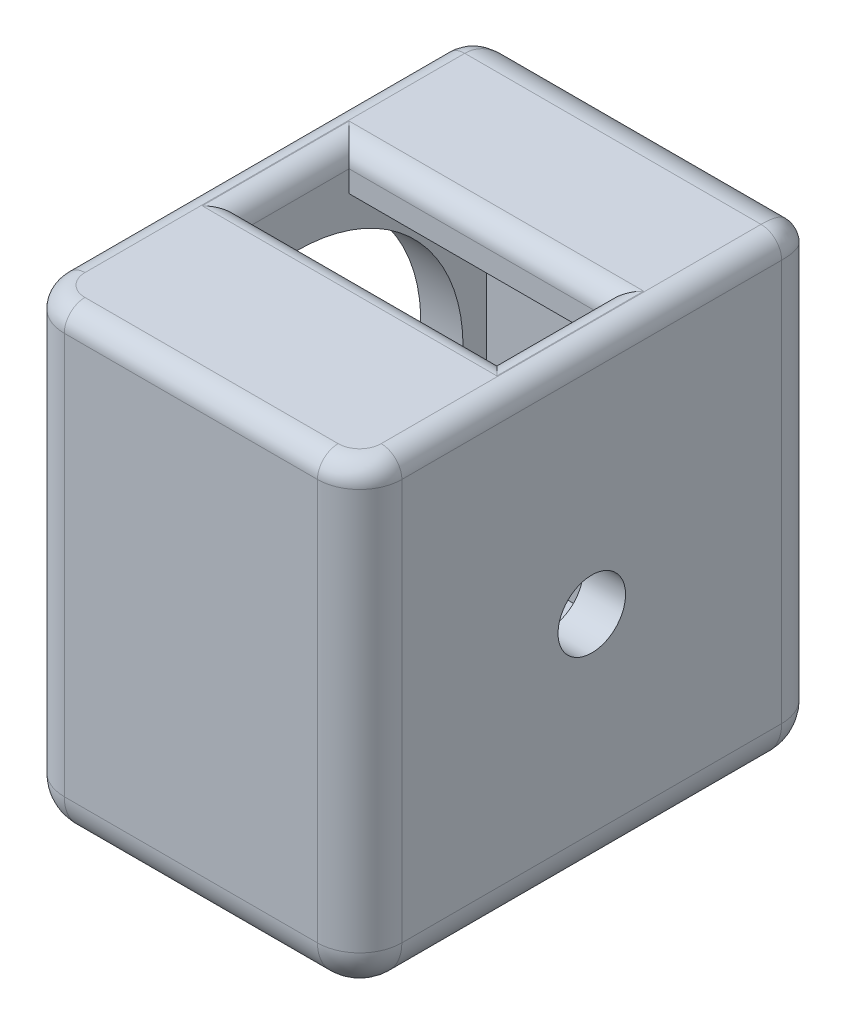
SolidWorks part; units mm, degrees
material "POLYURETHANE (11671)"
ref_plane "Front Plane" through (0, 0, 0) normal (0, 0, 1) x (1, 0, 0)
ref_plane "Top Plane" through (0, 0, 0) normal (0, 1, 0) x (1, 0, 0)
ref_plane "Right Plane" through (0, 0, 0) normal (1, 0, 0) x (0, 0, -1)
sketch "Sketch2" plane through (0, 0, 0) normal (0, 1, 0) x (1, 0, 0)
  line L0 (-7.62, 11.43) -> (-7.62, 13.97) construction
  line L1 (7.62, 11.43) -> (-7.62, 11.43)
  line L2 (7.62, 11.43) -> (7.62, -11.43)
  line L3 (7.62, -11.43) -> (-7.62, -11.43)
  line L4 (-7.62, 11.43) -> (-7.62, -11.43)
  line L5 (10.16, 13.97) -> (-10.16, 13.97)
  line L6 (10.16, 13.97) -> (10.16, -13.97)
  line L7 (10.16, -13.97) -> (-10.16, -13.97)
  line L8 (-10.16, 13.97) -> (-10.16, -13.97)
  line L9 (-7.62, 11.43) -> (-10.16, 11.43) construction
  point P8 (0, 13.97)
  point P9 (0, 11.43)
  point P11 (-7.62, 0)
  point P12 (-10.16, 0)
  dimension "D1" = 15.24
  dimension "D2" = 22.86
  dimension "D3" = 2.54
extrude "Boss-Extrude1" add sketch "Sketch2" along normal mid plane 27.94
sketch "Sketch3" plane through (0, -13.97, 0) normal (0, -1, 0) x (1, 0, 0)
  line L1 (-7.62, 11.43) -> (7.62, 11.43)
  line L2 (-7.62, 11.43) -> (-7.62, -11.43)
  line L3 (-7.62, -11.43) -> (7.62, -11.43)
  line L4 (7.62, 11.43) -> (7.62, -11.43)
extrude "Boss-Extrude2" add sketch "Sketch3" against normal blind 2.54
sketch "Sketch4" plane through (0, 13.97, 0) normal (0, 1, 0) x (1, 0, 0)
  line L0 (7.62, -11.43) -> (7.62, 11.43) construction
  line L1 (-7.62, 11.43) -> (7.62, 11.43)
  line L2 (-7.62, 11.43) -> (-7.62, 3.175)
  line L3 (-7.62, 3.175) -> (7.62, 3.175)
  line L4 (7.62, 11.43) -> (7.62, 3.175)
  line L11 (-7.62, -11.43) -> (7.62, -11.43) construction
  line L12 (-7.62, -11.43) -> (7.62, -11.43)
  line L13 (-7.62, -11.43) -> (-7.62, -3.175)
  line L14 (-7.62, -3.175) -> (7.62, -3.175)
  line L15 (7.62, -11.43) -> (7.62, -3.175)
  line L16 (7.62, -11.43) -> (-7.62, -11.43) construction
  dimension "D1" = 6.35
extrude "Boss-Extrude3" add sketch "Sketch4" against normal blind 2.54
sketch "Sketch5" plane through (-10.16, 0, 0) normal (-1, 0, 0) x (0, 0, 1)
  line L1 (-13.97, -13.97) -> (13.97, -13.97)
  line L2 (-13.97, -13.97) -> (-13.97, 13.97)
  line L3 (-13.97, 13.97) -> (13.97, 13.97)
  line L4 (13.97, -13.97) -> (13.97, 13.97)
  line L5 (-13.97, -13.97) -> (13.97, 13.97) construction
  line L6 (-13.97, 13.97) -> (13.97, -13.97) construction
  circle A0 centre (0, 0) radius 10.033
  point P0 (0, 0)
  dimension "D1" = 20.066
extrude "Cut-Extrude1" cut sketch "Sketch5" against normal up to surface (2.54 mm away) contours A0 up to face at (-7.62, 6.35, 0)
sketch "Sketch6" plane through (10.16, 0, 0) normal (1, 0, 0) x (0, 0, -1)
  line L1 (-13.97, -13.97) -> (13.97, -13.97)
  line L2 (-13.97, -13.97) -> (-13.97, 13.97)
  line L3 (-13.97, 13.97) -> (13.97, 13.97)
  line L4 (13.97, -13.97) -> (13.97, 13.97)
  line L5 (-13.97, -13.97) -> (13.97, 13.97) construction
  line L6 (-13.97, 13.97) -> (13.97, -13.97) construction
  circle A0 centre (0, 0) radius 2.032
  point P0 (0, 0)
  dimension "D1" = 4.064
extrude "Cut-Extrude2" cut sketch "Sketch6" against normal up to surface (2.54 mm away) contours A0 region at (10.16, 0, 0) up to face at (7.62, 6.35, 0)
sketch "Sketch7" plane through (0, 0, -13.97) normal (0, 0, -1) x (-1, 0, 0)
  line L0 (-10.16, 13.97) -> (-10.16, -13.97) construction
  line L1 (-4.445, -3.175) -> (-1.27, -3.175)
  line L2 (-4.445, -3.175) -> (-4.445, 3.175)
  line L3 (-4.445, 3.175) -> (-1.27, 3.175)
  line L4 (-1.27, -3.175) -> (-1.27, 3.175)
  line L5 (-4.445, -3.175) -> (-1.27, 3.175) construction
  line L6 (-4.445, 3.175) -> (-1.27, -3.175) construction
  point P0 (-2.8575, 0)
  dimension "D1" = 3.175
  dimension "D2" = 5.715
  dimension "D3" = 6.35
extrude "Cut-Extrude3" cut sketch "Sketch7" against normal up to surface (2.54 mm away) contours L4 L3 L2 L1 up to face at (0, 0, -11.43)
fillet "Fillet1" radius 2.54 9 edges at (-10.16, 0, -13.97) (-10.16, 0, 13.97) (10.16, 0, -13.97) (10.16, 0, 13.97) (0, 13.97, -13.97) (-10.16, -13.97, 0) (10.16, -13.97, 0) (0, -13.97, 13.97) (0, -13.97, -13.97)
fillet "Fillet2" radius 1.2446 11 edges at (-9.4161, 13.2261, -13.2261) (-10.16, 13.97, 0) (-9.4161, 13.97, 13.2261) (0, 13.97, 13.97) (9.4161, 13.97, 13.2261) (9.4161, 13.2261, -13.2261) (-7.62, 13.97, 0) (7.62, 13.97, 0) (0, 13.97, -3.175) (10.16, 13.97, 0) (0, 13.97, 3.175)
